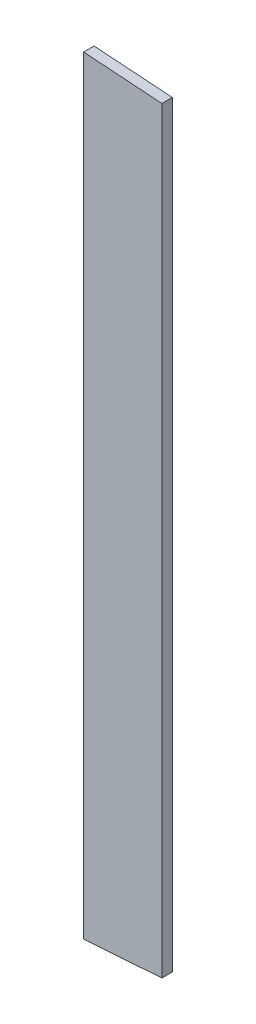
SolidWorks part; units mm, degrees
ref_plane "Front Plane" through (0, 0, 0) normal (0, 0, 1) x (1, 0, 0)
ref_plane "Top Plane" through (0, 0, 0) normal (0, 1, 0) x (1, 0, 0)
ref_plane "Right Plane" through (0, 0, 0) normal (1, 0, 0) x (0, 0, -1)
sketch "Sketch1" plane through (0, 0, 1306.1) normal (0, 0, 1) x (1, 0, 0)
  line L0 (-49.7697, 346.1083) -> (-64.7697, 345.0594)
  line L1 (-140.9262, 339.734) -> (58.5866, 353.6853) construction
  line L2 (-64.7697, 345.0594) -> (-64.7697, 492.4158)
  line L3 (58.5866, 483.7899) -> (-140.9262, 497.7412) construction
  line L4 (-64.7697, 492.4158) -> (-49.7697, 491.3669)
  line L5 (-49.7697, 491.3669) -> (-49.7697, 346.1083)
  dimension "D1" = 15
extrude "Boss-Extrude1" add sketch "Sketch1" along normal blind 2
ref_plane "Plane1" through (-57.2697, 0, 0) normal (1, 0, 0) x (0, 0, -1)
